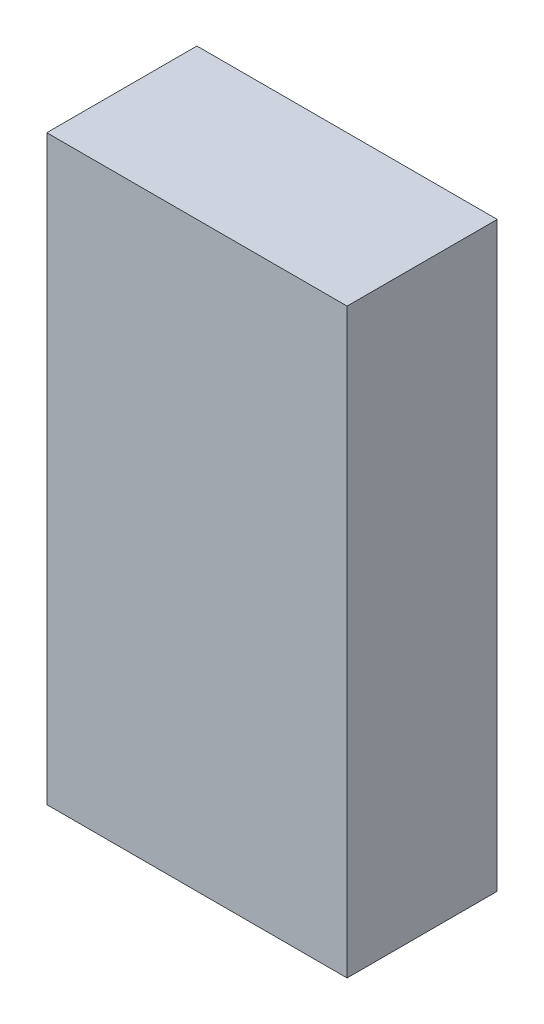
SolidWorks part; units mm, degrees
ref_plane "Front Plane" through (0, 0, 0) normal (0, 0, 1) x (1, 0, 0)
ref_plane "Top Plane" through (0, 0, 0) normal (0, 1, 0) x (1, 0, 0)
ref_plane "Right Plane" through (0, 0, 0) normal (1, 0, 0) x (0, 0, -1)
sketch "Sketch2" plane through (0, 0, 0) normal (0, 1, 0) x (1, 0, 0)
  line L1 (0, 0) -> (50.8, 0)
  line L2 (0, 0) -> (0, 25.4)
  line L3 (0, 25.4) -> (50.8, 25.4)
  line L4 (50.8, 0) -> (50.8, 25.4)
  dimension "D1" = 25.4
  dimension "D2" = 50.8
extrude "Boss-Extrude1" add sketch "Sketch2" along normal blind 98.425
sketch "Sketch4" plane through (0, 0, 0) normal (0, -1, 0) x (-1, 0, 0)
  line L0 (0, 0) -> (-50.8, 0) construction
  line L1 (-25.4, 0) -> (-25.4, 8.3981)
  circle A0 centre (-12.7, 12.7) radius 2.667
  circle A1 centre (-38.1, 12.7) radius 2.667
  dimension "D2" = 5.334
  dimension "D3" = 5.334
  dimension "D4" = 25.4
  dimension "D1" = 12.7
  dimension "D5" = 12.7
extrude "Cut-Extrude2" cut sketch "Sketch4" against normal blind 19.05 contours A0 | A1 region at (12.7, 0, -12.7) region at (38.1, 0, -12.7)
sketch "Sketch5" plane through (0, 0, -25.4) normal (0, 0, -1) x (-1, 0, 0)
  line L0 (-50.8, 98.425) -> (-50.8, 0) construction
  line L1 (-50.8, 98.425) -> (0, 98.425) construction
  circle A0 centre (-25.4, 85.725) radius 4.826
  dimension "D3" = 9.652
  dimension "D1" = 25.4
  dimension "D2" = 12.7
extrude "Cut-Extrude3" cut sketch "Sketch5" against normal blind 12.7
